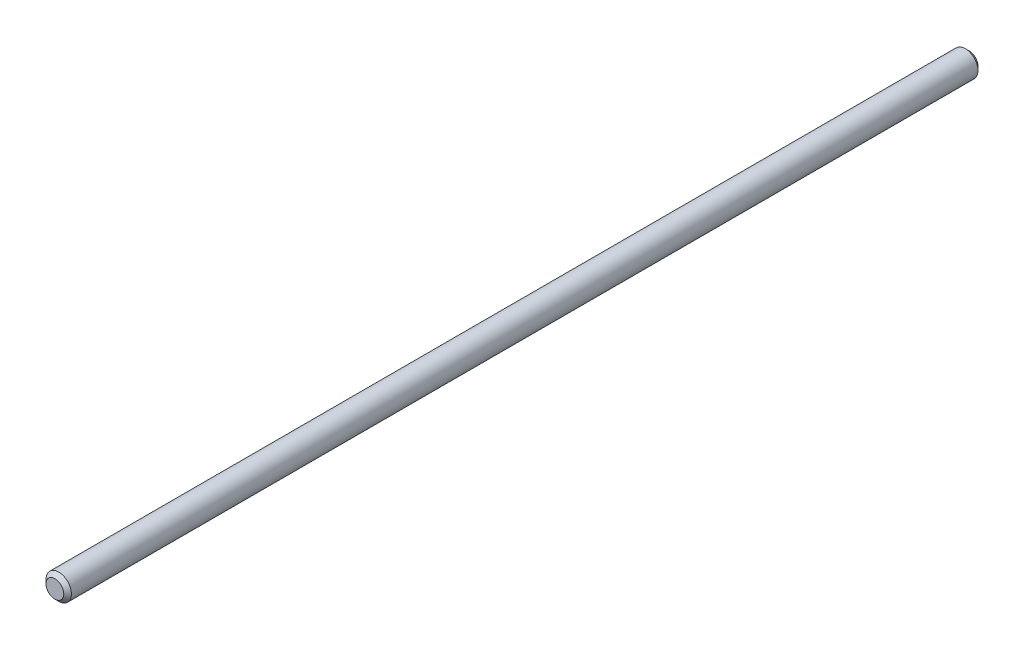
SolidWorks part; units mm, degrees
ref_plane "Front Plane" through (0, 0, 0) normal (0, 0, 1) x (1, 0, 0)
ref_plane "Top Plane" through (0, 0, 0) normal (0, 1, 0) x (1, 0, 0)
ref_plane "Right Plane" through (0, 0, 0) normal (1, 0, 0) x (0, 0, -1)
sketch "Sketch1" plane through (0, 0, 0) normal (1, 0, 0) x (0, 0, -1)
  line L0 (-114.3, 0) -> (114.3, 0) construction
  line L1 (-114.3, 0) -> (-114.3, 3.175)
  line L2 (-114.3, 3.175) -> (114.3, 3.175)
  line L3 (114.3, 3.175) -> (114.3, 0)
  line L4 (115.4906, 2.2126) -> (114.8556, 3.3125) construction
  line L5 (114.8556, 3.3125) -> (114.2206, 2.2126) construction
  line L6 (114.2206, 2.2126) -> (115.4906, 2.2126) construction
  line L7 (115.4113, 2.3501) -> (114.3, 2.3501) construction
  line L8 (114.8556, 2.2126) -> (114.8556, 2.3501) construction
  line L9 (114.8556, 2.3501) -> (114.8556, 3.175) construction
  line L10 (114.8556, 3.175) -> (114.8556, 3.3125) construction
  line L15 (114.935, 3.175) -> (114.7763, 3.175)
  line L16 (115.4509, 2.2814) -> (114.2603, 2.2814)
  line L17 (114.7763, 3.175) -> (114.2603, 2.2814)
  line L18 (114.935, 3.175) -> (115.4509, 2.2814)
  line L19 (114.3, 0) -> (114.3, -3.175) construction
  point P17 (114.8556, 2.2814)
  point P18 (101.6, 0)
  point P19 (111.76, -3.175)
  point P20 (63.5, 0)
  point P22 (-101.6, 0)
  dimension "Length" = 228.6
  dimension "Thread size" = 6.35
  dimension "Pitch" = 1.27
  dimension "D2" = 0.1588
  dimension "D1" = 2.54
  dimension "Segment" = 50.8
  dimension "D3" = 12.7
  dimension "D4" = 12.7
sketch "Sketch2" plane through (0, 0, 0) normal (1, 0, 0) x (0, 0, -1)
  line L0 (114.3, 3.175) -> (114.3, 0) construction
  line L1 (-114.3, 3.175) -> (114.3, 3.175) construction
  line L2 (-114.3, 0) -> (-114.3, 3.175) construction
  line L3 (114.3, 3.175) -> (114.3, 0)
  line L4 (-114.3, 3.175) -> (114.3, 3.175)
  line L5 (-114.3, 0) -> (-114.3, 3.175)
  line L6 (-114.3, 0) -> (114.3, 0)
revolve "Revolve1" add sketch "Sketch2" angle 360 about L6
chamfer "Chamfer1" distance 0.9525 angle 45 2 edges at (3.175, 0, -114.3) (3.175, 0, 114.3)
sketch "Sketch3" [suppressed] plane through (0, 0, -152.4) normal (0, 0, -1) x (-1, 0, 0)
  circle A0 centre (0, 0) radius 2.3501
extrude "Cut-Extrude1" [suppressed] cut sketch "Sketch3" against normal through all flip side to cut
sketch "Sketch4" [suppressed] plane through (0, 0, -152.4) normal (0, 0, -1) x (-1, 0, 0)
  circle A1 centre (0, 0) radius 2.3501
  circle A2 centre (0, 0) radius 2.3501
  dimension "D1" = 0
ref_plane "Plane1" [suppressed] through (0, 0, 152.4) normal (0, 0, 1) x (1, 0, 0)
curve "Helix/Spiral1" [suppressed] pitch 1.27 height 52.07 turns 41
sketch "Sketch5" [suppressed] plane through (0, 0, 0) normal (1, 0, 0) x (0, 0, -1)
  line L0 (153.035, 3.175) -> (152.8762, 3.175) construction
  line L1 (152.8762, 3.175) -> (152.3603, 2.2814) construction
  line L2 (153.5509, 2.2814) -> (152.3603, 2.2814) construction
  line L3 (153.035, 3.175) -> (153.5509, 2.2814) construction
  line L4 (153.035, 3.175) -> (152.8762, 3.175)
  line L5 (152.8762, 3.175) -> (152.3603, 2.2814)
  line L6 (153.5509, 2.2814) -> (152.3603, 2.2814)
  line L7 (153.035, 3.175) -> (153.5509, 2.2814)
sweep "Sweep1" [suppressed] add profiles "Sketch5" path "Helix/Spiral1"
pattern_linear "LPattern1" [suppressed] count 6 spacing 50.8 along (0, 0, 1) of bodies 136
other "SurfaceCut1" [suppressed]
sketch "Sketch6" [suppressed] plane through (0, 0, 0) normal (1, 0, 0) x (0, 0, -1)
  line L0 (152.4, 2.2225) -> (151.4475, 3.175)
  line L1 (152.4, 3.175) -> (152.4, 0) construction
  line L3 (-152.4, 3.175) -> (152.4, 3.175) construction
  line L4 (151.4475, 3.175) -> (151.4475, 3.3125)
  line L5 (151.4475, 3.3125) -> (153.5906, 3.3125)
  line L6 (153.5906, 3.3125) -> (153.5906, 2.2225)
  line L7 (153.5906, 2.2225) -> (152.4, 2.2225)
  dimension "D1" = 45
  dimension "D2" = 0.9525
revolve "Cut-Revolve1" [suppressed] cut sketch "Sketch6" angle 360 about L0
mirror "Mirror1" [suppressed] about plane through (0, 0, 0) normal (0, 0, 1)
equation "\"D2@Sketch1\"=\"Pitch@Sketch1\"/8"
equation "\"D2@Sketch1\" = \"Pitch@Sketch1\" / 8"
equation "\"D1@Sketch1\"=\"Pitch@Sketch1\"*2"
equation "\"Segment@Sketch1\" = \"Pitch@Sketch1\" * 40"
equation "\"D4@Sketch1\"=\"D3@Sketch1\""
equation "\"D1@Chamfer1\"=\"pitch@sketch1\"*0.75"
equation "\"D3@Helix/Spiral1\"=\"segment@sketch1\"+\"pitch@sketch1\""
equation "\"D4@Helix/Spiral1\"=\"pitch@sketch1\""
equation "\"D3@LPattern1\"=\"segment@sketch1\""
equation "\"D1@LPattern1\"=\"length@sketch1\"/\"segment@sketch1\"+1"
equation "\"D2@Sketch6\"=\"pitch@sketch1\"*0.75"
